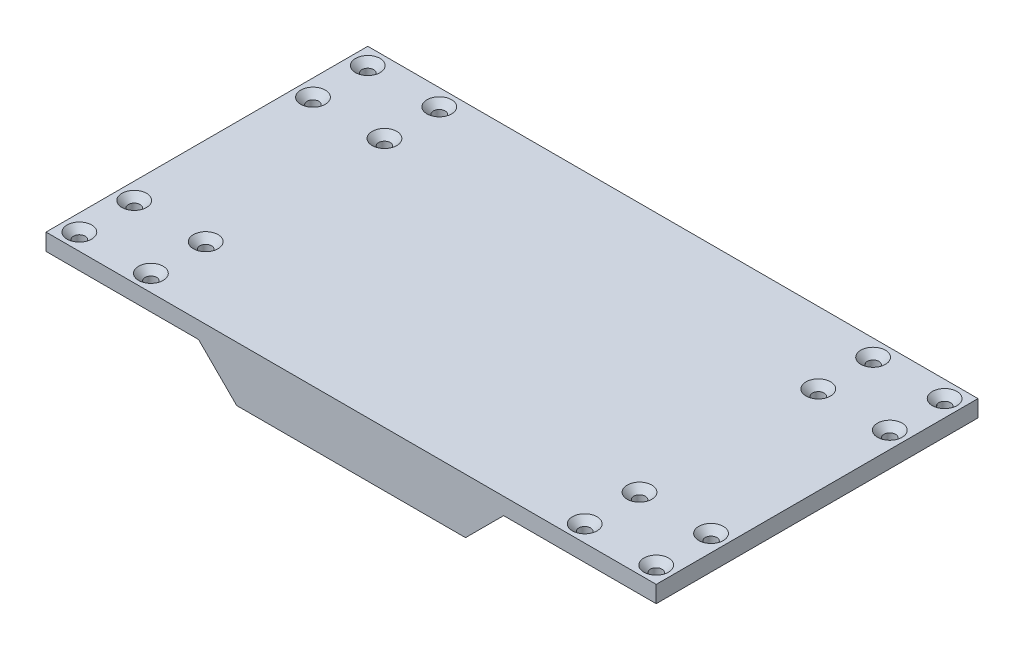
SolidWorks part; units mm, degrees
ref_plane "Front Plane" through (0, 0, 0) normal (0, 0, 1) x (1, 0, 0)
ref_plane "Top Plane" through (0, 0, 0) normal (0, 1, 0) x (1, 0, 0)
ref_plane "Right Plane" through (0, 0, 0) normal (1, 0, 0) x (0, 0, -1)
sketch "Sketch1" plane through (0, 0, 0) normal (0, 1, 0) x (1, 0, 0)
  line L1 (0, 0) -> (203.2, 0)
  line L2 (0, 0) -> (0, 107.1562)
  line L3 (0, 107.1562) -> (203.2, 107.1562)
  line L4 (203.2, 0) -> (203.2, 107.1562)
  dimension "D1" = 203.2
  dimension "D2" = 107.1562
extrude "Boss-Extrude1" add sketch "Sketch1" along normal blind 5.588
hole_wizard "CSK for M3.5 Flat Head Machine Screw1" positions "Sketch2" profile "Sketch3" countersink size "M3.5" standard "ANSI Metric" end condition through all
sketch "Sketch2" plane through (0, 5.588, 0) normal (0, 1, 0) x (1, 0, 0)
  line L0 (0, 101.6) -> (203.2, 101.6)
  line L1 (0, 107.1562) -> (0, 0) construction
  line L2 (203.2, 0) -> (203.2, 107.1562) construction
  line L5 (5.5562, 0) -> (5.5563, 107.1562)
  line L6 (0, 0) -> (203.2, 0) construction
  line L7 (203.2, 107.1562) -> (0, 107.1562) construction
  line L10 (29.3687, 107.1562) -> (29.3688, 0)
  line L13 (0, 5.5562) -> (203.2, 5.5562)
  line L16 (197.6437, 0) -> (197.6437, 107.1562)
  line L19 (173.8312, 0) -> (173.8312, 107.1562)
  line L21 (0, 83.3438) -> (203.2, 83.3438)
  line L24 (0, 23.8125) -> (203.2, 23.8125)
  point P0 (5.5562, 101.6)
  point P40 (1.2015, 116.4001)
  point P42 (1.2015, 113.37)
  point P45 (29.3687, 101.6)
  point P47 (5.5563, 5.5562)
  point P49 (29.3688, 5.5562)
  point P51 (173.8312, 5.5562)
  point P53 (173.8312, 101.6)
  point P55 (197.6437, 101.6)
  point P57 (197.6437, 5.5562)
  point P67 (5.5563, 83.3438)
  point P69 (29.3688, 83.3438)
  point P71 (5.5563, 23.8125)
  point P72 (173.8312, 83.3438)
  point P74 (197.6437, 83.3438)
  point P76 (173.8312, 23.8125)
  point P78 (197.6437, 23.8125)
  point P80 (29.3688, 23.8125)
  dimension "D1" = 5.5562
  dimension "D2" = 23.8125
  dimension "D3" = 5.5562
  dimension "D4" = 5.5562
  dimension "D5" = 23.8125
  dimension "D6" = 5.5562
  dimension "D7" = 18.2562
  dimension "D8" = 18.2562
sketch "Sketch3" plane through (5.5562, 5.588, -101.6) normal (1, 0, 0) x (0, 0, 1)
  line L0 (0, 0) -> (0, 5.588)
  line L1 (0, 5.588) -> (1.95, 5.588)
  line L2 (1.95, 5.588) -> (1.95, 2.15)
  line L3 (1.95, 2.15) -> (4.1, 0)
  line L5 (4.1, 0) -> (0, 0)
  line L6 (-1.95, 2.15) -> (-4.1, 0) construction
  line L11 (0, -6.35) -> (0, 107.95) construction
  dimension "Thru Hole Dia." = 3.9
  dimension "Thru Hole Depth" = 5.588
  dimension "Near C'Sink Dia." = 8.2
  dimension "Near C'Sink Angle" = 90
sketch "Sketch4" plane through (0, 0, 0) normal (0, -1, 0) x (1, 0, 0)
  line L0 (0, 0) -> (203.2, 0) construction
  line L1 (50.8, 0) -> (152.4, 0)
  line L2 (50.8, 0) -> (50.8, -107.1562)
  line L3 (50.8, -107.1562) -> (152.4, -107.1562)
  line L4 (152.4, 0) -> (152.4, -107.1562)
  line L5 (203.2, -107.1562) -> (0, -107.1562) construction
  line L6 (50.8, -53.5781) -> (0, -53.5781) construction
  line L8 (0, -107.1562) -> (0, 0) construction
  line L10 (152.4, -53.5781) -> (203.2, -53.5781) construction
  line L11 (203.2, 0) -> (203.2, -107.1562) construction
  dimension "D1" = 101.6
ref_plane "Plane1" through (0, -12.7, 0) normal (0, -1, 0) x (-1, 0, 0)
sketch "Sketch5" plane through (0, -12.7, 0) normal (0, -1, 0) x (-1, 0, 0)
  line L0 (-50.8, 107.1562) -> (-152.4, 107.1562) construction
  line L1 (-139.7, 107.1562) -> (-63.5, 107.1562)
  line L2 (-139.7, 107.1562) -> (-139.7, 0)
  line L3 (-139.7, 0) -> (-63.5, 0)
  line L4 (-63.5, 107.1562) -> (-63.5, 0)
  line L5 (-50.8, 0) -> (-152.4, 0) construction
  line L8 (-203.2, 53.5781) -> (-139.7, 53.5781) construction
  line L10 (-203.2, 0) -> (-203.2, 107.1562) construction
  line L11 (-63.5, 53.5781) -> (0, 53.5781) construction
  dimension "D1" = 76.2
loft "Loft4" add profiles "Sketch4", "Sketch5" connector at (152.4, 0, -107.1562) connector at (139.7, -12.7, -107.1562)
